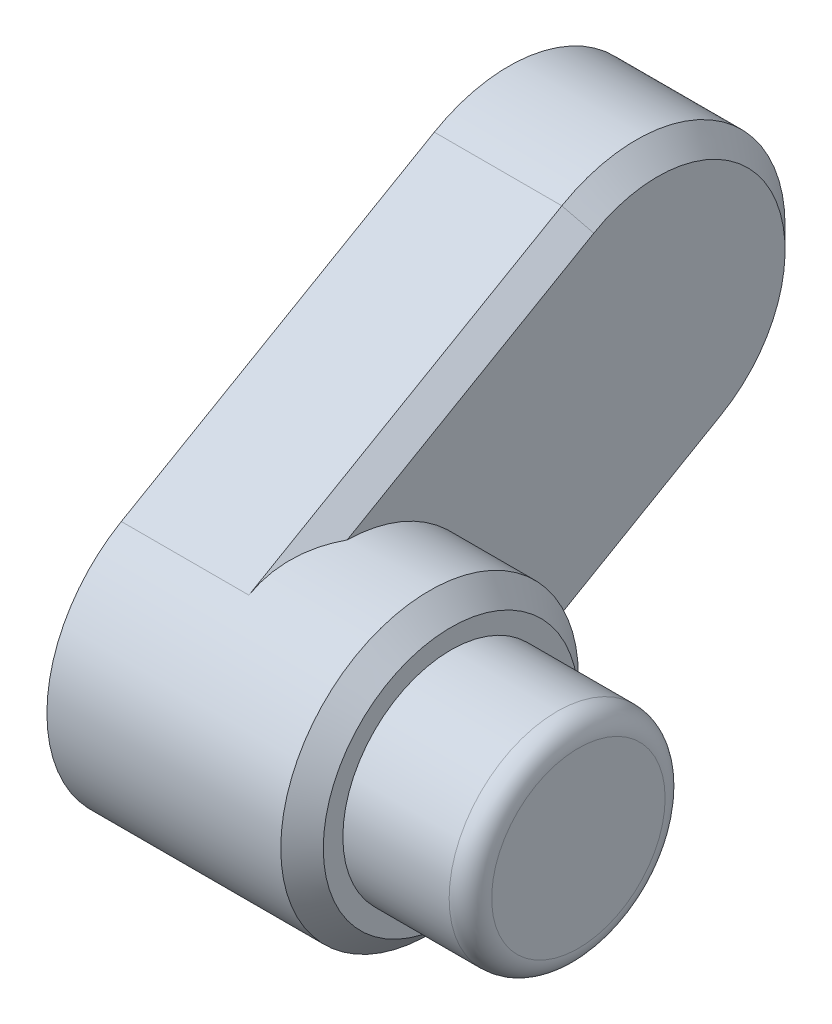
SolidWorks part; units mm, degrees
ref_plane "Front Plane" through (0, 0, 0) normal (0, 0, 1) x (1, 0, 0)
ref_plane "Top Plane" through (0, 0, 0) normal (0, 1, 0) x (1, 0, 0)
ref_plane "Right Plane" through (0, 0, 0) normal (1, 0, 0) x (0, 0, -1)
sketch "Sketch1" plane through (0, 0, 0) normal (1, 0, 0) x (0, 0, -1)
  line L0 (0, 0) -> (147.2243, 85) construction
  line L1 (-35, 60.6218) -> (112.2243, 145.6218)
  line L2 (35, -60.6218) -> (182.2243, 24.3782)
  line L3 (0, 0) -> (146.3593, 0)
  arc A0 (-35, 60.6218) -> (35, -60.6218) centre (0, 0) ccw
  arc A1 (182.2243, 24.3782) -> (112.2243, 145.6218) centre (147.2243, 85) ccw
  point P3 (73.6122, 42.5)
  dimension "D3" = 70
  dimension "D1" = 30
  dimension "D2" = 170
extrude "Boss-Extrude1" add sketch "Sketch1" along normal blind 70 contours L2 A1 L1 A0 region at (0, 42.5, -73.6122)
sketch "Sketch2" plane through (70, 0, 0) normal (1, 0, 0) x (0, 0, -1)
  circle A0 centre (0, 0) radius 12.7
  dimension "D1" = 25.4
extrude "Boss-Extrude2" add sketch "Sketch2" along normal blind 10
sketch "Sketch3" plane through (80, 0, 0) normal (1, 0, 0) x (0, 0, -1)
  circle A0 centre (0, 0) radius 25.4
  dimension "D1" = 50.8
extrude "Boss-Extrude3" add sketch "Sketch3" along normal blind 10
sketch "Sketch4" plane through (90, 0, 0) normal (1, 0, 0) x (0, 0, -1)
  circle A0 centre (0, 0) radius 50.8
  dimension "D1" = 101.6
extrude "Boss-Extrude4" add sketch "Sketch4" along normal blind 90
sketch "Sketch5" plane through (70, 0, 0) normal (1, 0, 0) x (0, 0, -1)
  circle A0 centre (0, 0) radius 70
  arc A1 (-35, 60.6218) -> (35, -60.6218) centre (0, 0) ccw construction
  circle A2 centre (0, 0) radius 50.8
  dimension "D1" = 0
extrude "Boss-Extrude5" add sketch "Sketch5" along normal blind 50
fillet "Fillet1" radius 10 1 edges at (180, 0, -50.8)
chamfer "Chamfer1" distance 10 angle 45 4 edges at (70, -18.1218, -108.6122) (70, 120, -207.8461) (70, 103.1218, -38.6122) (120, 0, -70)
